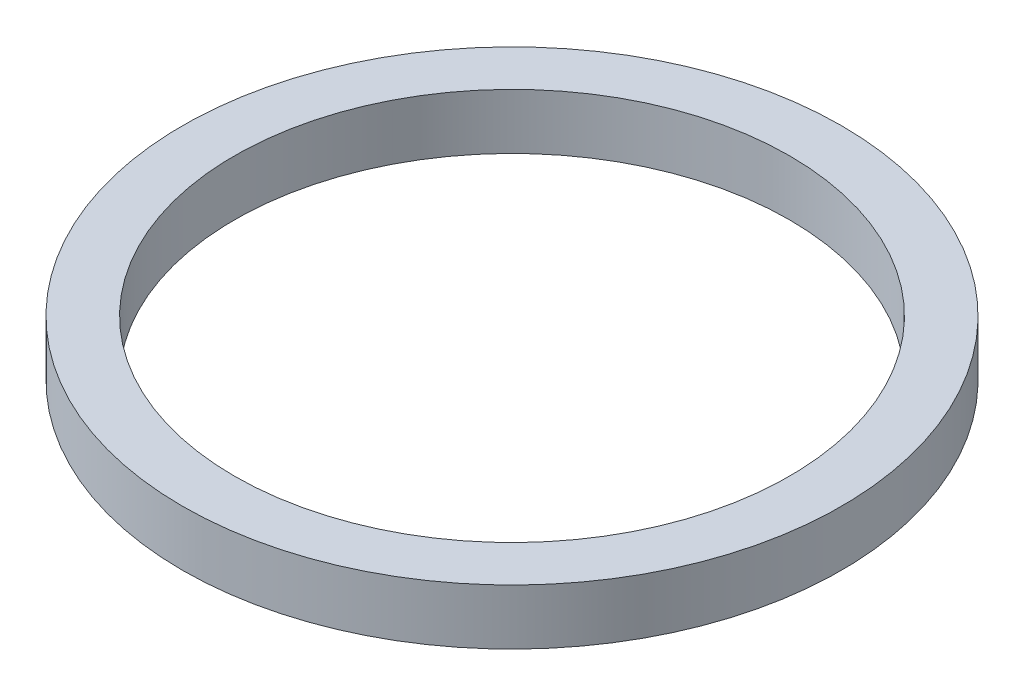
SolidWorks part; units mm, degrees
ref_plane "Front Plane" through (0, 0, 0) normal (0, 0, 1) x (1, 0, 0)
ref_plane "Top Plane" through (0, 0, 0) normal (0, 1, 0) x (1, 0, 0)
ref_plane "Right Plane" through (0, 0, 0) normal (1, 0, 0) x (0, 0, -1)
sketch "Sketch1" plane through (0, 0, 0) normal (0, 1, 0) x (1, 0, 0)
  circle A0 centre (0, 0) radius 47.5
  dimension "FLANGE_OD" = 95
extrude "Boss-Extrude1" add sketch "Sketch1" along normal blind 8
sketch "Sketch2" plane through (0, 0, 0) normal (0, 1, 0) x (1, 0, 0)
  circle A0 centre (0, 0) radius 40
  dimension "BORE_D" = 80
extrude "Cut-Extrude1" cut sketch "Sketch2" along normal through all
sketch "Sketch3" plane through (0, 8, 0) normal (0, 1, 0) x (1, 0, 0)
  circle A0 centre (0, 0) radius 22.2135 construction
  circle A1 centre (-22.2135, 0) radius 1.5
  dimension "BOLT_D" = 3
  dimension "BOLT_PCD" = 44.4271
extrude "Cut-Extrude2" cut sketch "Sketch3" against normal blind 5.0391 rebuild error yes
pattern_circular "CirPattern1" count 3 over 360 rebuild error yes
